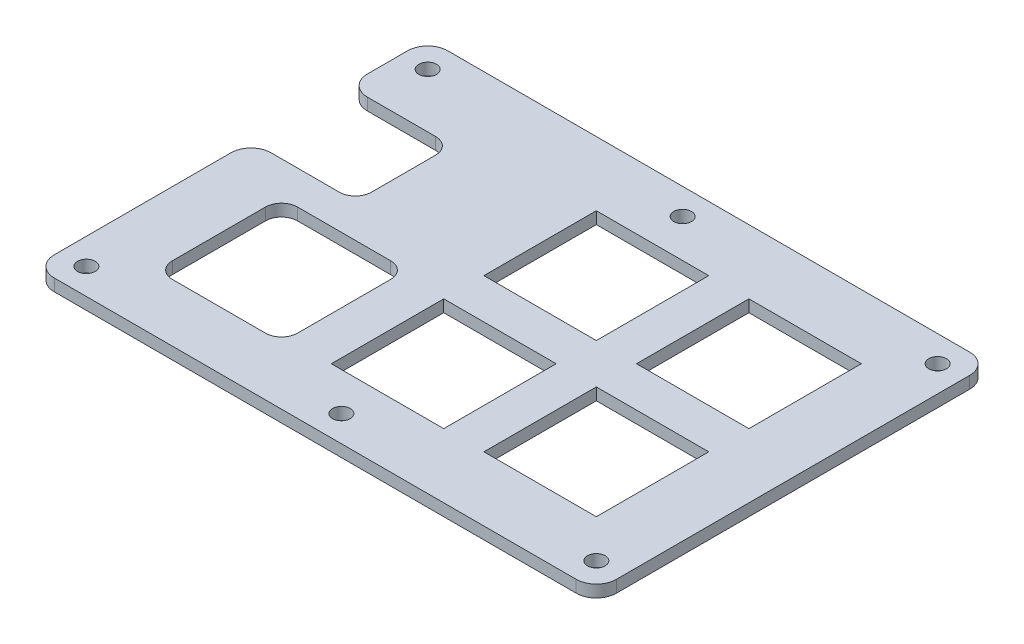
SolidWorks part; units mm, degrees
ref_plane "Front Plane" through (0, 0, 0) normal (0, 0, 1) x (1, 0, 0)
ref_plane "Top Plane" through (0, 0, 0) normal (0, 1, 0) x (1, 0, 0)
ref_plane "Right Plane" through (0, 0, 0) normal (1, 0, 0) x (0, 0, -1)
sketch "Sketch1" plane through (0, 0, 0) normal (0, 1, 0) x (1, 0, 0)
  line L1 (20, -19.5) -> (-20, -19.5)
  line L2 (20, -19.5) -> (20, 19.5)
  line L3 (20, 19.5) -> (-20, 19.5)
  line L4 (-20, -19.5) -> (-20, 19.5)
  line L5 (20, -19.5) -> (-20, 19.5) construction
  line L6 (20, 19.5) -> (-20, -19.5) construction
  point P0 (0, 0)
  dimension "D1" = 39
  dimension "D2" = 40
extrude "Boss-Extrude1" add sketch "Sketch1" along normal blind 1.5
sketch "Sketch3" plane through (0, 0, 0) normal (0, 1, 0) x (1, 0, 0)
  line L0 (25, 24.5) -> (-45, 24.5)
  line L1 (-45, 24.5) -> (-45, -24.5)
  line L2 (-45, -24.5) -> (25, -24.5)
  line L3 (25, -24.5) -> (25, 24.5)
  line L4 (20, -19.5) -> (20, 19.5) construction
  line L5 (25, 0) -> (0, 0) construction
  dimension "D1" = 70
  dimension "D2" = 49
  dimension "D3" = 5
extrude "Boss-Extrude2" add sketch "Sketch3" along normal up to surface (1.5 mm away) up to face at (0, 1.5, 0)
sketch "Sketch4" plane through (0, 1.5, 0) normal (0, 1, 0) x (1, 0, 0)
  line L0 (25, 24.5) -> (-45, 24.5) construction
  line L1 (-45, 14.5) -> (-32, 14.5)
  line L2 (-45, 14.5) -> (-45, 2.5)
  line L3 (-45, 2.5) -> (-32, 2.5)
  line L4 (-32, 14.5) -> (-32, 2.5)
  line L5 (-45, 14.5) -> (-32, 2.5) construction
  line L6 (-10, 24.5) -> (-10, -24.5) construction
  line L7 (-45, -24.5) -> (25, -24.5) construction
  line L8 (-45, 24.5) -> (-45, -24.5) construction
  point P6 (-38.5, 8.5)
  dimension "D1" = 13
  dimension "D2" = 12
  dimension "D4" = 8.5
extrude "Cut-Extrude1" cut sketch "Sketch4" against normal through all
sketch "Sketch5" plane through (0, 1.5, 0) normal (0, 1, 0) x (1, 0, 0)
  line L1 (-37, -1.7) -> (-21.4, -1.7)
  line L2 (-37, -1.7) -> (-37, -17.3)
  line L3 (-37, -17.3) -> (-21.4, -17.3)
  line L4 (-21.4, -1.7) -> (-21.4, -17.3)
  line L5 (-37, -1.7) -> (-21.4, -17.3) construction
  line L6 (-10, -24.5) -> (-10, 24.5) construction
  line L7 (-45, -24.5) -> (25, -24.5) construction
  line L8 (25, 24.5) -> (-45, 24.5) construction
  point P6 (-29.2, -9.5)
  dimension "D1" = 15.6
  dimension "D2" = 19.2
  dimension "D3" = 9.5
extrude "Cut-Extrude2" cut sketch "Sketch5" against normal through all
fillet "Fillet2" radius 2 4 edges at (-37, 0.75, 17.3) (-21.4, 0.75, 17.3) (-21.4, 0.75, 1.7) (-37, 0.75, 1.7)
sketch "Sketch6" plane through (0, 1.5, 0) normal (0, 1, 0) x (1, 0, 0)
  line L0 (-45, 24.5) -> (-45, 14.5) construction
  line L1 (-41.75, 21.25) -> (21.75, 21.25) construction
  line L2 (-41.75, 21.25) -> (-41.75, -21.25) construction
  line L3 (-41.75, -21.25) -> (21.75, -21.25) construction
  line L4 (21.75, 21.25) -> (21.75, -21.25) construction
  line L5 (25, -24.5) -> (25, 24.5) construction
  line L6 (-45, -24.5) -> (25, -24.5) construction
  line L7 (25, 24.5) -> (-45, 24.5) construction
  line L8 (-10, 21.25) -> (-10, -21.25) construction
  line L9 (-41.75, 0) -> (-10, 0) construction
  line L10 (-10, 0) -> (21.75, 0) construction
  circle A0 centre (-41.75, 21.25) radius 1.1
  circle A1 centre (21.75, 21.25) radius 1.1
  circle A2 centre (21.75, -21.25) radius 1.1
  circle A3 centre (-41.75, -21.25) radius 1.1
  circle A4 centre (-10, -21.25) radius 1.1
  circle A5 centre (-10, 21.25) radius 1.1
  dimension "D5" = 2.2
  dimension "D1" = 3.25
  dimension "D2" = 3.25
  dimension "D3" = 3.25
  dimension "D4" = 3.25
  dimension "D6" = 42.5
extrude "Cut-Extrude3" cut sketch "Sketch6" against normal through all
fillet "Fillet4" radius 2.5 6 edges at (25, 0.75, -24.5) (-45, 0.75, 24.5) (-45, 0.75, -24.5) (25, 0.75, 24.5) (-45, 0.75, -2.5) (-45, 0.75, -14.5)
sketch "Sketch7" plane through (0, 1.5, 0) normal (0, 1, 0) x (1, 0, 0)
  line L0 (-44.2678, -23.7678) -> (24.2678, 23.7678) construction
  line L1 (-16, 16.5) -> (-2, 16.5)
  line L2 (-16, 16.5) -> (-16, 2.5)
  line L3 (-16, 2.5) -> (-2, 2.5)
  line L4 (-2, 16.5) -> (-2, 2.5)
  line L5 (-16, 16.5) -> (-2, 2.5) construction
  line L6 (-16, 2.5) -> (-2, 16.5) construction
  arc A0 (-45, -22) -> (-42.5, -24.5) centre (-42.5, -22) ccw construction
  arc A1 (25, 22) -> (22.5, 24.5) centre (22.5, 22) ccw construction
  point P0 (-9, 9.5)
  point P13 (-10, 0)
  dimension "D1" = 1
  dimension "D2" = 9.5
  dimension "D3" = 14
  dimension "D4" = 14
extrude "Cut-Extrude4" cut sketch "Sketch7" against normal through all
pattern_linear "LPattern1" count 2 spacing 19 along (1, 0, 0) count 2 spacing 19 along (0, 0, 1) of "Cut-Extrude4"
fillet "Fillet5" radius 2 2 edges at (-32, 0.75, -14.5) (-32, 0.75, -2.5)
equation "\"D3@Sketch5\"=19/2"
